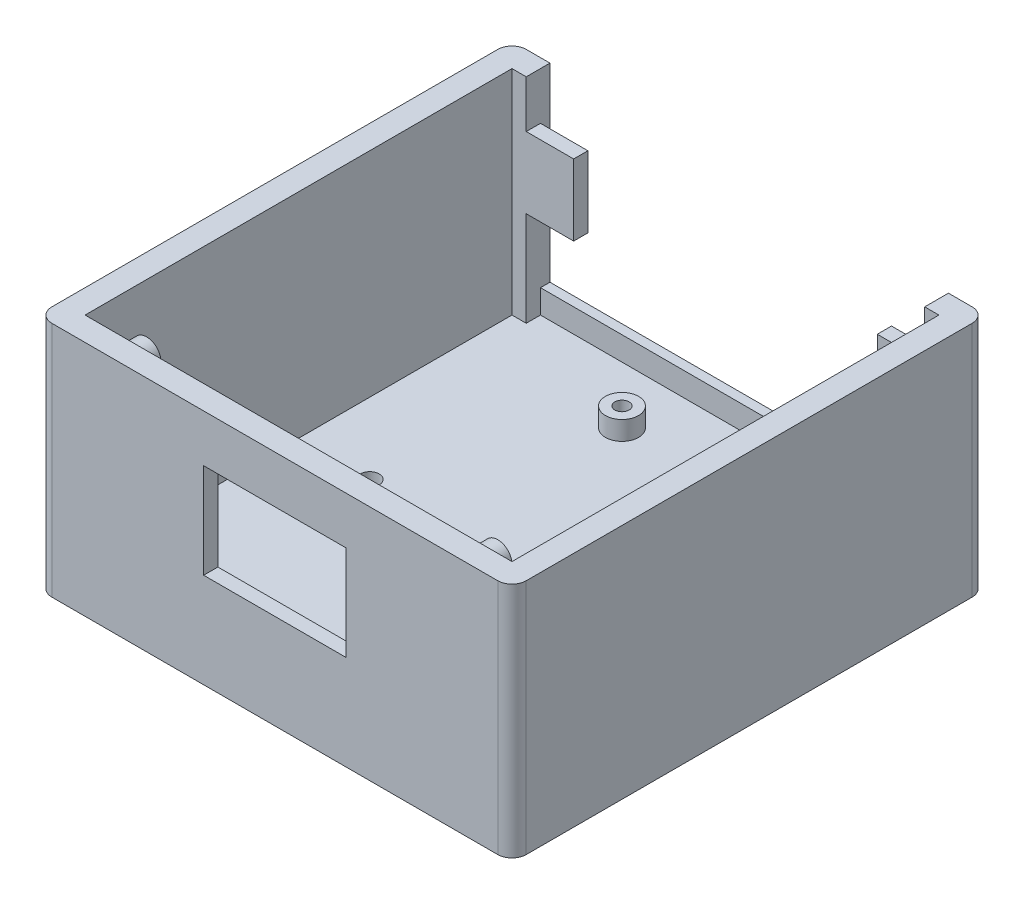
SolidWorks part; units mm, degrees
ref_plane "前视基准面" through (0, 0, 0) normal (0, 0, 1) x (1, 0, 0)
ref_plane "上视基准面" through (0, 0, 0) normal (0, 1, 0) x (1, 0, 0)
ref_plane "右视基准面" through (0, 0, 0) normal (1, 0, 0) x (0, 0, -1)
sketch "草图1" plane through (0, 0, 0) normal (0, 1, 0) x (1, 0, 0)
  line L1 (3, 0) -> (97, 0)
  line L2 (0, 3) -> (0, 97)
  line L3 (3, 100) -> (97, 100)
  line L4 (100, 3) -> (100, 97)
  arc A0 (0, 97) -> (3, 100) centre (3, 97) cw
  arc A1 (97, 100) -> (100, 97) centre (97, 97) cw
  arc A2 (97, 0) -> (100, 3) centre (97, 3) ccw
  arc A3 (0, 3) -> (3, 0) centre (3, 3) ccw
  point P7 (0, 100)
  point P12 (100, 0)
  point P15 (0, 0)
  dimension "D3" = 3
  dimension "D1" = 100
  dimension "D2" = 100
extrude "外壳主要形状" add sketch "草图1" along normal blind 50
ref_plane "基准面1" through (50, 0, 0) normal (1, 0, 0) x (0, 0, -1)
sketch "草图2" plane through (0, 50, 0) normal (0, 1, 0) x (1, 0, 0)
  line L0 (100, 3) -> (100, 97) construction
  line L1 (5, 5) -> (95, 5)
  line L2 (5, 5) -> (5, 95)
  line L3 (5, 95) -> (95, 95)
  line L4 (95, 5) -> (95, 95)
  line L5 (0, 97) -> (0, 3) construction
  line L6 (3, 0) -> (97, 0) construction
  line L7 (97, 100) -> (3, 100) construction
  dimension "D1" = 5
  dimension "D2" = 5
  dimension "D3" = 5
  dimension "D4" = 5
extrude "外壳内空间" cut sketch "草图2" against normal blind 45
sketch "草图3" plane through (0, 5, 0) normal (0, 1, 0) x (1, 0, 0)
  line L0 (37.1875, 86) -> (62.8125, 86) construction
  line L1 (95, 95) -> (5, 95) construction
  circle A0 centre (37.1875, 86) radius 1.5
  circle A1 centre (37.1875, 86) radius 3.5
  circle A2 centre (62.8125, 86) radius 1.5
  circle A3 centre (62.8125, 86) radius 3.5
  point P6 (50, 86)
  point P9 (50, 95)
  dimension "D1" = 3
  dimension "D2" = 7
  dimension "D3" = 3
  dimension "D4" = 7
  dimension "D5" = 9
  dimension "D6" = 25.625
extrude "TYPE-C固定螺柱" add sketch "草图3" along normal blind 4
extrude "TYPE-C固定延长" cut sketch "草图3<2>" against normal blind 2 contours A0 | A2 region at (37.1875, 5, -86) region at (62.8125, 5, -86)
sketch "草图3<2>" plane through (0, 5, 0) normal (0, 1, 0) x (1, 0, 0) same geometry as "草图3"
sketch "草图4" plane through (0, 0, -95) normal (0, 0, 1) x (1, 0, 0)
  line L0 (66.3125, 9) -> (59.3125, 9) construction
  line L1 (31.6875, 8) -> (68.3125, 8)
  line L2 (31.6875, 8) -> (31.6875, 18)
  line L3 (31.6875, 18) -> (68.3125, 18)
  line L4 (68.3125, 8) -> (68.3125, 18)
  line L5 (66.3125, 5) -> (66.3125, 9) construction
  line L6 (33.6875, 9) -> (33.6875, 5) construction
  line L7 (95, 5) -> (5, 5) construction
  dimension "D1" = 1
  dimension "D2" = 2
  dimension "D3" = 2
  dimension "D4" = 10
extrude "TYPE-C板口" cut sketch "草图4" against normal blind 3
sketch "草图5" plane through (0, 0, -98) normal (0, 0, 1) x (1, 0, 0)
  line L0 (31.6875, 8) -> (68.3125, 8) construction
  line L1 (45, 10) -> (55, 10)
  line L2 (45, 10) -> (45, 15)
  line L3 (45, 15) -> (55, 15)
  line L4 (55, 10) -> (55, 15)
  line L7 (50, 10) -> (50, 15) construction
  line L8 (50, -27.5) -> (50, 27.5) construction
  dimension "D1" = 10
  dimension "D2" = 2
  dimension "D3" = 5
extrude "TYPE-C口" cut sketch "草图5" against normal blind 2
sketch "草图6" plane through (0, 0, -5) normal (0, 0, -1) x (-1, 0, 0)
  line L0 (-5, 5) -> (-5, 50) construction
  line L1 (-5, 50) -> (-95, 50) construction
  line L2 (-5, 5) -> (-95, 5) construction
  line L3 (-95, 5) -> (-95, 50) construction
  circle A0 centre (-13, 10.5) radius 1.5
  circle A1 centre (-13, 44.5) radius 1.5
  circle A2 centre (-87, 44.5) radius 1.5
  circle A3 centre (-87, 24.5) radius 1.5
  circle A4 centre (-87, 44.5) radius 3
  circle A5 centre (-87, 24.5) radius 3
  circle A6 centre (-13, 44.5) radius 3
  circle A7 centre (-13, 10.5) radius 3
  dimension "D1" = 3
  dimension "D2" = 8
  dimension "D3" = 5.5
  dimension "D6" = 19.5
  dimension "D7" = 3
  dimension "D8" = 6
  dimension "D4" = 5.5
  dimension "D5" = 8
extrude "主板固定螺柱" add sketch "草图6" along normal blind 5
sketch "草图7" plane through (0, 0, 0) normal (0, 0, 1) x (1, 0, 0)
  line L0 (3, 0) -> (97, 0) construction
  line L1 (35, 20) -> (65, 20)
  line L2 (35, 20) -> (35, 40)
  line L3 (35, 40) -> (65, 40)
  line L4 (65, 20) -> (65, 40)
  line L5 (100, 50) -> (100, 0) construction
  dimension "D1" = 30
  dimension "D2" = 20
  dimension "D3" = 20
  dimension "D4" = 35
extrude "OLED屏口" cut sketch "草图7" against normal blind 5
sketch "草图8" plane through (0, 0, -5) normal (0, 0, -1) x (-1, 0, 0)
  line L0 (-35, 40) -> (-35, 20) construction
  line L1 (-72, 47) -> (-28, 47)
  line L2 (-72, 47) -> (-72, 13)
  line L3 (-72, 13) -> (-28, 13)
  line L4 (-28, 47) -> (-28, 13)
  line L5 (-65, 40) -> (-35, 40) construction
  line L6 (-35, 20) -> (-65, 20) construction
  line L7 (-65, 20) -> (-65, 40) construction
  dimension "D1" = 7
  dimension "D2" = 7
  dimension "D3" = 7
  dimension "D4" = 7
extrude "OLED屏板口" cut sketch "草图8" against normal blind 2
sketch "草图9" plane through (0, 0, 0) normal (0, -1, 0) x (1, 0, 0)
  line L0 (3, 0) -> (97, 0) construction
  line L1 (80, -50) -> (20, -50) construction
  line L2 (0, -97) -> (0, -3) construction
  circle A0 centre (80, -50) radius 4
  circle A1 centre (80, -50) radius 2
  circle A2 centre (20, -50) radius 4
  circle A3 centre (20, -50) radius 2
  point P8 (50, -50)
  dimension "D1" = 50
  dimension "D2" = 4
  dimension "D3" = 8
  dimension "D5" = 60
  dimension "D4" = 50
extrude "上下连接螺丝头隐藏口" cut sketch "草图9" against normal blind 2.5
extrude "上下连接螺丝口" cut sketch "草图9<2>" against normal blind 5 contours A1 | A3 region at (80, 0, -50)
sketch "草图9<2>" plane through (0, 0, 0) normal (0, -1, 0) x (1, 0, 0) same geometry as "草图9"
sketch "草图10" plane through (0, 0, -100) normal (0, 0, -1) x (-1, 0, 0)
  line L0 (-97, 50) -> (-3, 50) construction
  line L1 (-92, 10) -> (-8, 10)
  line L2 (-92, 10) -> (-92, 50)
  line L3 (-92, 50) -> (-8, 50)
  line L4 (-8, 10) -> (-8, 50)
  line L5 (-45, 10) -> (-55, 10) construction
  line L6 (-3, 50) -> (-3, 0) construction
  line L7 (-97, 50) -> (-97, 0) construction
  dimension "D1" = 5
  dimension "D2" = 5
extrude "切除-拉伸9" cut sketch "草图10" against normal up to surface (5 mm away) up to face at (50, 13, -95)
sketch "草图11" plane through (0, 10, 0) normal (0, 1, 0) x (1, 0, 0)
  line L1 (68.3125, 98) -> (92, 98)
  line L2 (68.3125, 98) -> (68.3125, 95)
  line L3 (68.3125, 95) -> (92, 95)
  line L4 (92, 98) -> (92, 95)
  line L5 (31.6875, 98) -> (8, 98)
  line L6 (31.6875, 98) -> (31.6875, 95)
  line L7 (31.6875, 95) -> (8, 95)
  line L8 (8, 98) -> (8, 95)
extrude "切除-拉伸10" cut sketch "草图11" against normal up to surface (2 mm away) up to face at (50, 8, -96.5)
sketch "草图12" plane through (0, 8, 0) normal (0, 1, 0) x (1, 0, 0)
  line L1 (92, 95) -> (8, 95)
  line L2 (92, 95) -> (92, 98)
  line L3 (92, 98) -> (8, 98)
  line L4 (8, 95) -> (8, 98)
extrude "切除-拉伸11" cut sketch "草图12" against normal up to surface (3 mm away) up to face at (80, 5, -52)
sketch "草图14" plane through (0, 50, 0) normal (0, 1, 0) x (1, 0, 0)
  line L0 (92, 98) -> (8, 98) construction
  line L1 (8, 95) -> (18, 95)
  line L2 (8, 95) -> (8, 98)
  line L3 (8, 98) -> (18, 98)
  line L4 (18, 95) -> (18, 98)
  line L6 (92, 95) -> (82, 95)
  line L7 (92, 95) -> (92, 98)
  line L8 (92, 98) -> (82, 98)
  line L9 (82, 95) -> (82, 98)
  dimension "D1" = 10
  dimension "D2" = 10
extrude "凸台-拉伸1" add sketch "草图14" against normal blind 25
extrude "切除-拉伸12" cut sketch "草图14<2>" against normal blind 10
sketch "草图14<2>" plane through (0, 50, 0) normal (0, 1, 0) x (1, 0, 0) same geometry as "草图14"
